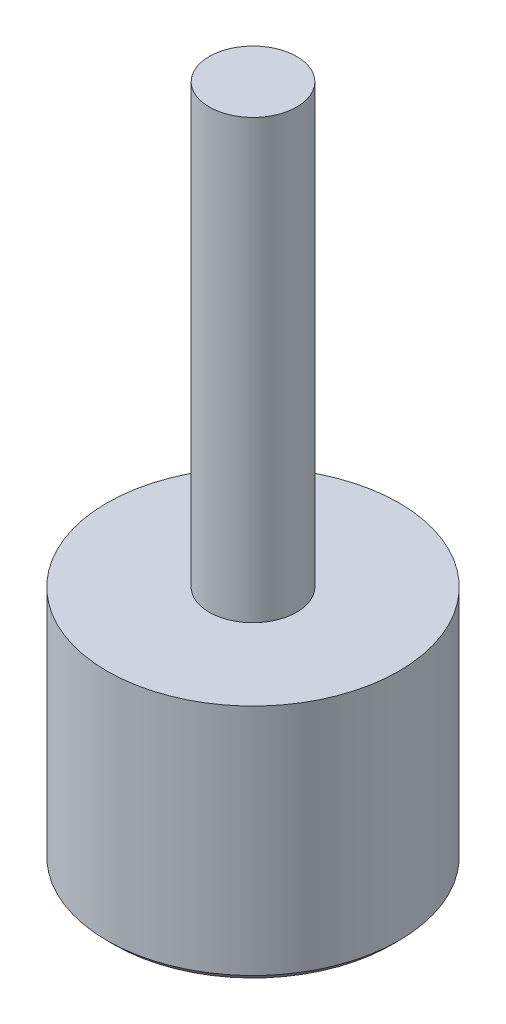
SolidWorks part; units mm, degrees
ref_plane "Plan de face" through (0, 0, 0) normal (0, 0, 1) x (1, 0, 0)
ref_plane "Plan de dessus" through (0, 0, 0) normal (0, 1, 0) x (1, 0, 0)
ref_plane "Plan de droite" through (0, 0, 0) normal (1, 0, 0) x (0, 0, -1)
sketch "Esquisse1" plane through (0, 0, 0) normal (0, 1, 0) x (1, 0, 0)
  circle A0 centre (0, 0) radius 10
  circle A1 centre (0, 0) radius 3.5
  dimension "D2" = 7
extrude "Boss.-Extru.1" add sketch "Esquisse1" along normal blind 4
sketch "Esquisse2" plane through (0, 0, 0) normal (0, -1, 0) x (1, 0, 0)
  circle A0 centre (0, 0) radius 10
  circle A1 centre (0, 0) radius 6.75
  dimension "D1" = 13.5
extrude "Boss.-Extru.2" add sketch "Esquisse2" along normal blind 10
sketch "Esquisse5" plane through (0, 0, 0) normal (1, 0, 0) x (0, 0, -1)
  line L0 (-6.25, -10.5) -> (-9.5, -10.5)
  line L1 (-9.5, -10.5) -> (-10, -10)
  line L2 (-6.25, -10.5) -> (-6.75, -10)
  line L3 (-10, -10) -> (-7.7896, -10) construction
  line L4 (-6.25, -10.5) -> (-6.25, -5.311) construction
  line L5 (-10, -10) -> (-6.75, -10)
  line L6 (-6.75, -10) -> (-10, -10)
  line L7 (0, 0) -> (0, -10.8152) construction
  dimension "D1" = 0.5
  dimension "D2" = 45
  dimension "D3" = 45
  dimension "D4" = 90
revolve "Révolution2" add sketch "Esquisse5" angle 360 about L7 region at (0, -10.25, 8.125)
sketch "Esquisse7" plane through (0, 0, 0) normal (0, -1, 0) x (1, 0, 0)
  line L0 (-3.261, 1.2713) -> (-6.289, 2.4518)
  line L1 (-6.6953, 0.8575) -> (-3.4716, 0.4446)
  line L2 (0, 0) -> (-6.0564, 1.5436) construction
  line L3 (1.2713, 3.261) -> (2.4518, 6.289)
  line L4 (0.8575, 6.6953) -> (0.4446, 3.4716)
  line L5 (0, 0) -> (1.5436, 6.0564) construction
  line L6 (3.261, -1.2713) -> (6.289, -2.4518)
  line L7 (6.6953, -0.8575) -> (3.4716, -0.4446)
  line L8 (0, 0) -> (6.0564, -1.5436) construction
  line L9 (-1.2713, -3.261) -> (-2.4518, -6.289)
  line L10 (-0.8575, -6.6953) -> (-0.4446, -3.4716)
  line L11 (0, 0) -> (-1.5436, -6.0564) construction
  circle A0 centre (0, 0) radius 3.5 construction
  arc A1 (-6.289, 2.4518) -> (-6.6953, 0.8575) centre (0, 0) ccw
  circle A2 centre (0, 0) radius 6.75 construction
  arc A3 (-3.4716, 0.4446) -> (-3.261, 1.2713) centre (0, 0) cw
  arc A4 (2.4518, 6.289) -> (0.8575, 6.6953) centre (0, 0) ccw
  arc A5 (6.289, -2.4518) -> (6.6953, -0.8575) centre (0, 0) ccw
  arc A6 (-2.4518, -6.289) -> (-0.8575, -6.6953) centre (0, 0) ccw
  point P30 (0, 0)
  circle M3 centre (0, 0) radius 3.5
  circle M4 centre (0, 0) radius 6.75
  dimension "D1" = 7
  dimension "D2" = 7
  dimension "D3" = 4
extrude "Boss.-Extru.3" add sketch "Esquisse7" along normal blind 1.5 contours L1 L0 M4 M3 | L10 L9 M4 M3 | L7 L6 M4 M3 | L4 L3 M4 M3 region at (-5.1199, 0, 1.3049) region at (1.3049, 0, 5.1199) region at (-1.3049, 0, -5.1199) region at (5.1199, 0, -1.3049)
fillet "Congé1" radius 2 8 edges at (-4.775, 0, 1.8615) (-5.0835, 0, 0.6511) (0.6511, 0, 5.0835) (1.8615, 0, 4.775) (5.0835, 0, -0.6511) (4.775, 0, -1.8615) (-0.6511, 0, -5.0835) (-1.8615, 0, -4.775)
sketch "Esquisse13" plane through (0, 4, 0) normal (0, 1, 0) x (1, 0, 0)
  circle A0 centre (0, 0) radius 3.5
extrude "Boss.-Extru.6" add sketch "Esquisse13" against normal blind 2
sketch "Esquisse15" plane through (0, 4, 0) normal (0, 1, 0) x (1, 0, 0)
  circle A0 centre (0, 0) radius 10
extrude "Boss.-Extru.7" add sketch "Esquisse15" along normal blind 2
sketch "Esquisse21" plane through (0, 6, 0) normal (0, 1, 0) x (1, 0, 0)
  circle A0 centre (0, 0) radius 3
extrude "Boss.-Extru.8" add sketch "Esquisse21" along normal blind 30
